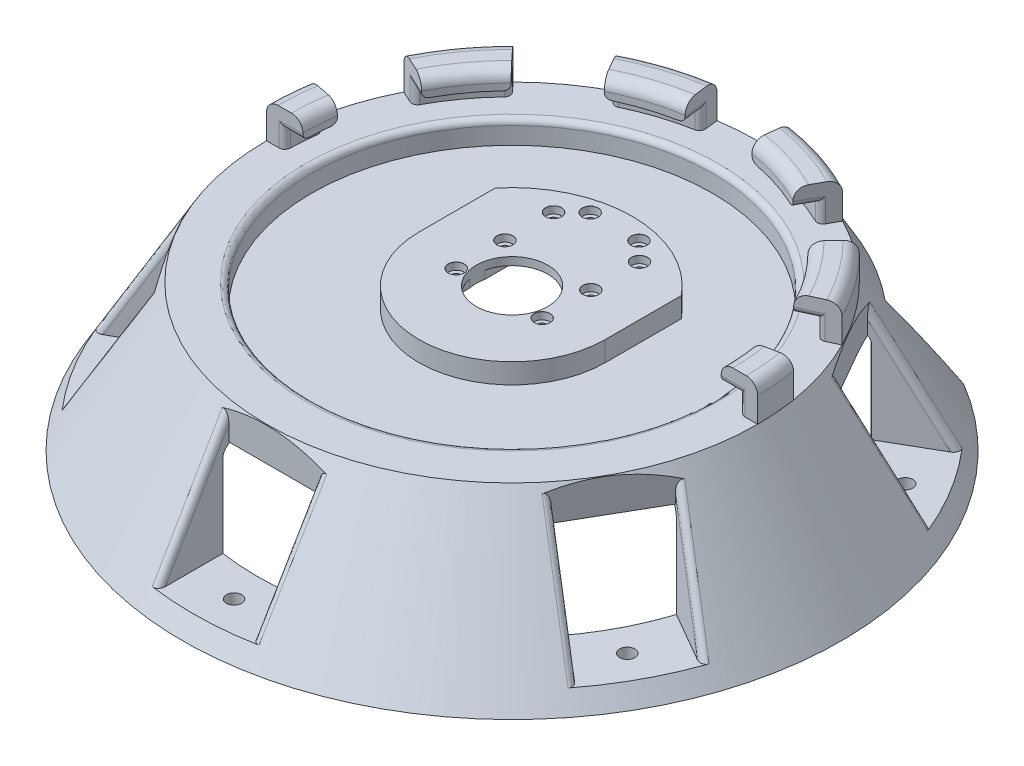
SolidWorks part; units mm, degrees
material "PLA"
ref_plane "Front Plane" through (0, 0, 0) normal (0, 0, 1) x (1, 0, 0)
ref_plane "Top Plane" through (0, 0, 0) normal (0, 1, 0) x (1, 0, 0)
ref_plane "Right Plane" through (0, 0, 0) normal (1, 0, 0) x (0, 0, -1)
sketch "Sketch1" plane through (0, 0, 0) normal (0, 0, 1) x (1, 0, 0)
  line L0 (0, 0) -> (-85.725, 0)
  line L1 (-85.725, 0) -> (-115.0544, -50.8)
  line L2 (-115.0544, -50.8) -> (0, -50.8)
  line L6 (0, 0) -> (0, -50.8) construction
  line L7 (0, 0) -> (0, -50.8)
  dimension "D1" = 85.725
  dimension "D3" = 50.8
  dimension "D4" = 60
revolve "Revolve1" add sketch "Sketch1" angle 360 about L6
sketch "Sketch2" plane through (0, 0, 0) normal (0, 1, 0) x (1, 0, 0)
  circle A0 centre (0, 0) radius 12.5
  dimension "D1" = 25
extrude "Cut-Extrude1" cut sketch "Sketch2" against normal through all
sketch "Sketch3" plane through (0, 0, 0) normal (0, 1, 0) x (1, 0, 0)
  line L0 (-32.5, 0) -> (-32.5, 26.6036)
  line L1 (-32.5, 26.6036) -> (32.5, 26.6036)
  line L2 (32.5, 26.6036) -> (32.5, 0)
  circle A0 centre (0, 0) radius 32.5
  circle A1 centre (0, 0) radius 70
  circle A2 centre (0, 0) radius 42
  circle M1 centre (0, 0) radius 12.5
  dimension "D1" = 65
  dimension "D2" = 140
  dimension "D3" = 84
extrude "Cut-Extrude2" cut sketch "Sketch3" against normal blind 8 contours A1 A0 L0 L1 L2 | A1 A2 region at (0, 0, 33.5845) region at (-68.0201, 0, 0)
sketch "Sketch7" plane through (0, -50.8, 0) normal (0, -1, 0) x (1, 0, 0)
  line L0 (3.6132, 88.8265) -> (-2.6643, -115.0235) construction
  line L1 (-88.0643, 0) -> (82.7357, 0) construction
  line L2 (-62.6643, -63.0586) -> (-62.6643, -115.0235)
  line L3 (-62.6643, -115.0235) -> (57.3357, -115.0235)
  line L4 (57.3357, -115.0235) -> (57.3357, -67.9399)
  arc A2 (57.3357, -67.9399) -> (-62.6643, -63.0586) centre (0, 0) ccw
  circle A3 centre (0, 0) radius 115.0544 construction
  dimension "D1" = 177.8
  dimension "D2" = 25.4
  dimension "D3" = 25.4
  dimension "D4" = 120
  dimension "D5" = 88.9
extrude "Cut-Extrude5" cut sketch "Sketch7" against normal blind 39 contours L3 L4 A2 L2
sketch "Sketch8" plane through (0, 0, 0) normal (0, 1, 0) x (1, 0, 0)
  line L0 (0, 0) -> (3.123, -115.012) construction
  line L2 (-13.0273, -123.925) -> (18.7227, -123.925)
  line L3 (-13.0273, -123.925) -> (-13.0273, -85.825)
  line L4 (-13.0273, -85.825) -> (18.7227, -85.825)
  line L5 (18.7227, -123.925) -> (18.7227, -85.825)
  line L6 (-13.0273, -123.925) -> (18.7227, -85.825) construction
  line L7 (-13.0273, -85.825) -> (18.7227, -123.925) construction
  arc A0 (-62.6643, 96.4919) -> (57.3357, 99.7504) centre (0, 0) ccw construction
  point P6 (2.8477, -104.875)
  dimension "D1" = 85.825
  dimension "D2" = 38.1
  dimension "D3" = 31.75
extrude "Cut-Extrude6" cut sketch "Sketch8" against normal blind 44.45
pattern_circular "CirPattern2" count 6 over 360 about axis through (0, 0, 0) along (0, 1, 0) of "Cut-Extrude6" reverse direction yes
sketch "Sketch9" plane through (0, 0, 0) normal (0, 1, 0) x (1, 0, 0)
  line L0 (0, 0) -> (3.123, -115.012) construction
  arc A0 (-62.6643, 96.4919) -> (57.3357, 99.7504) centre (0, 0) ccw construction
  circle A1 centre (2.7092, -99.772) radius 2.65
  dimension "D1" = 5.3
  dimension "D2" = 15.24
extrude "Cut-Extrude7" cut sketch "Sketch9" against normal through all
pattern_circular "CirPattern3" count 6 over 360 about axis through (0, 0, 0) along (0, 1, 0) of "Cut-Extrude7"
sketch "Sketch12" plane through (0, 0, 0) normal (0, 0, 1) x (1, 0, 0)
  line L0 (85.725, 0) -> (85.725, 12.7)
  line L1 (85.725, 12.7) -> (73.025, 12.7)
  line L2 (73.025, 12.7) -> (73.025, 6.35)
  line L3 (73.025, 6.35) -> (79.375, 6.35)
  line L4 (79.375, 6.35) -> (79.375, 0)
  line L5 (85.725, 0) -> (-85.725, 0) construction
  line L6 (0, 0) -> (0, 12.7) construction
  line L7 (12.5, 0) -> (-12.5, 0) construction
  line L8 (79.375, 0) -> (85.725, 0)
  point P13 (0, 6.35)
  point P14 (0, 0)
  dimension "D1" = 6.35
  dimension "D2" = 73.025
  dimension "D3" = 79.375
  dimension "D4" = 12.7
  dimension "D5" = 12.7
revolve "Revolve2" add sketch "Sketch12" angle 180 about L6
sketch "Sketch15" plane through (0, -11.8, 0) normal (0, -1, 0) x (1, 0, 0)
  line L0 (0, -1000) -> (0, 49000) construction
  point P1 (-15, 4.5)
  point P4 (-15, -12.5)
  point P5 (-15, -29.5)
  point P6 (-8.5, -35.8)
  point P7 (8.5, -35.8)
  point P8 (15, -29.5)
  point P9 (15, -12.5)
  point P10 (15, 4.5)
  dimension "D1" = 17
  dimension "D2" = 17
  dimension "D3" = 4.5
  dimension "D4" = 15
  dimension "D5" = 8.5
  dimension "D6" = 35.8
sketch "Sketch18" plane through (0, 12.7, 0) normal (0, 1, 0) x (1, 0, 0)
  line L0 (46.6433, 89.7185) -> (70.9138, 72.0849)
  line L1 (0, 201000) -> (0, -249000) construction
  line L2 (-15, 100) -> (-9, 50)
  line L3 (-9, 50) -> (9, 50)
  line L4 (9, 50) -> (15, 100)
  line L5 (-15, 100) -> (15, 100)
  line L6 (36.6704, 35.1608) -> (70.9138, 72.0849)
  line L7 (22.1081, 45.7409) -> (36.6704, 35.1608)
  line L8 (46.6433, 89.7185) -> (22.1081, 45.7409)
  line L9 (90.4704, 45.1675) -> (99.7409, 16.6359)
  line L10 (50.334, 6.8913) -> (99.7409, 16.6359)
  line L11 (44.7717, 24.0104) -> (50.334, 6.8913)
  line L12 (90.4704, 45.1675) -> (44.7717, 24.0104)
  line L13 (99.7409, -16.6359) -> (90.4704, -45.1675)
  line L14 (44.7717, -24.0104) -> (90.4704, -45.1675)
  line L15 (50.334, -6.8913) -> (44.7717, -24.0104)
  line L16 (99.7409, -16.6359) -> (50.334, -6.8913)
  line L17 (70.9138, -72.0849) -> (46.6433, -89.7185)
  line L18 (22.1081, -45.7409) -> (46.6433, -89.7185)
  line L19 (36.6704, -35.1608) -> (22.1081, -45.7409)
  line L20 (70.9138, -72.0849) -> (36.6704, -35.1608)
  line L21 (15, -100) -> (-15, -100)
  line L22 (-9, -50) -> (-15, -100)
  line L23 (9, -50) -> (-9, -50)
  line L24 (15, -100) -> (9, -50)
  line L25 (-46.6433, -89.7185) -> (-70.9138, -72.0849)
  line L26 (-36.6704, -35.1608) -> (-70.9138, -72.0849)
  line L27 (-22.1081, -45.7409) -> (-36.6704, -35.1608)
  line L28 (-46.6433, -89.7185) -> (-22.1081, -45.7409)
  line L29 (-90.4704, -45.1675) -> (-99.7409, -16.6359)
  line L30 (-50.334, -6.8913) -> (-99.7409, -16.6359)
  line L31 (-44.7717, -24.0104) -> (-50.334, -6.8913)
  line L32 (-90.4704, -45.1675) -> (-44.7717, -24.0104)
  line L33 (-99.7409, 16.6359) -> (-90.4704, 45.1675)
  line L34 (-44.7717, 24.0104) -> (-90.4704, 45.1675)
  line L35 (-50.334, 6.8913) -> (-44.7717, 24.0104)
  line L36 (-99.7409, 16.6359) -> (-50.334, 6.8913)
  line L37 (-70.9138, 72.0849) -> (-46.6433, 89.7185)
  line L38 (-22.1081, 45.7409) -> (-46.6433, 89.7185)
  line L39 (-36.6704, 35.1608) -> (-22.1081, 45.7409)
  line L40 (-70.9138, 72.0849) -> (-36.6704, 35.1608)
  point P4 (0, 50)
  point P7 (0, 100)
  point P48 (0, 0)
  dimension "D1" = 18
  dimension "D2" = 50
  dimension "D3" = 30
  dimension "D4" = 50
  dimension "D5" = 10
extrude "Cut-Extrude9" cut sketch "Sketch18" against normal blind 12.7
sketch "Sketch20" plane through (0, -11.8, 0) normal (0, -1, 0) x (1, 0, 0)
  line L0 (-22.5, -33) -> (-12.5, -40)
  line L1 (22.5, 20) -> (-22.5, 20)
  line L2 (22.5, 20) -> (22.5, -40)
  line L3 (22.5, -40) -> (-22.5, -40)
  line L4 (-22.5, 20) -> (-22.5, -40)
  line L5 (22.5, 20) -> (-22.5, -40) construction
  line L6 (22.5, -40) -> (-22.5, 20) construction
  line L7 (-12.5, -40) -> (12.5, -40)
  line L8 (12.5, -40) -> (22.5, -33)
  point P0 (0, -10)
  line M11 (-13.0268, 13) -> (13.0268, 13)
  line M12 (13.0268, 13) -> (13.0268, -34)
  line M13 (13.0268, -34) -> (-13.0268, -34)
  line M14 (-13.0268, -34) -> (-13.0268, 13)
  dimension "D1" = 60
  dimension "D2" = 45
  dimension "D3" = 10
  dimension "D4" = 10
  dimension "D5" = 7
  dimension "D6" = 7
  dimension "D7" = 10
extrude "Cut-Extrude11" cut sketch "Sketch3<3>" against normal blind 1 contours A0 L1 M1 | A0 L1 L0 | L1 A0 | L1 A2 A0 | A0 L2 L1 | A0 region at (-28.056, 0, -14.587) region at (-28.5629, 0, -20.2686) region at (0, 0, -33.9353) region at (28.5629, 0, -20.2686) region at (0, 0, -28.9815)
sketch "Sketch3<3>" plane through (0, 0, 0) normal (0, 1, 0) x (1, 0, 0) same geometry as "Sketch3"
sketch "Sketch22" plane through (0, -1, 0) normal (0, 1, 0) x (1, 0, 0)
  circle A0 centre (-15, 12.5) radius 1.4
  circle A1 centre (-15, 29.5) radius 1.4
  circle A2 centre (-8.5, 35.8) radius 1.4
  circle A3 centre (8.5, 35.8) radius 1.4
  circle A4 centre (15, 29.5) radius 1.4
  circle A5 centre (15, 12.5) radius 1.4
  circle A6 centre (15, -4.5) radius 1.4
  circle A7 centre (-15, -4.5) radius 1.4
hole_wizard "CBORE for M2.5 SHCS1" positions "Sketch23" profile "Sketch24" counterbore size "M2.5" standard "ANSI Metric" end condition through all
sketch "Sketch23" plane through (0, -1, 0) normal (0, 1, 0) x (1, 0, 0)
  point P0 (-15, -4.5)
  point P3 (-15, 12.5)
  point P6 (-15, 29.5)
  point P9 (-8.5, 35.8)
  point P12 (8.5, 35.8)
  point P15 (15, 29.5)
  point P18 (15, 12.5)
  point P21 (15, -4.5)
sketch "Sketch24" plane through (-15, -1, 4.5) normal (1, 0, 0) x (0, 0, 1)
  line L0 (0, 0) -> (0, 49.8)
  line L1 (0, 49.8) -> (1.45, 49.8)
  line L3 (1.45, 49.8) -> (1.45, 2.5)
  line L4 (2.75, 2.5) -> (1.45, 2.5)
  line L5 (2.75, 2.5) -> (2.75, 0.025)
  line L6 (2.75, 0.025) -> (2.775, 0)
  line L7 (2.775, 0) -> (0, 0)
  line L8 (-2.75, 0.025) -> (-2.775, 0) construction
  line L11 (0, -6.35) -> (0, 107.95) construction
  dimension "Thru Hole Dia." = 2.9
  dimension "Thru Hole Depth" = 49.8
  dimension "C'Bore Dia." = 5.5
  dimension "C'Bore Depth" = 2.5
  dimension "Near C'Sink Dia." = 5.55
  dimension "Near C'Sink Angle" = 90
fillet "Fillet1" radius 4 12 edges at (85.4509, 12.7, -6.8497) (69.353, 12.7, -50.3879) (26.4905, 12.7, -81.5293) (-26.4905, 12.7, -81.5293) (-69.353, 12.7, -50.3879) (-85.4509, 12.7, -6.8497) (-72.8088, 12.7, -5.6148) (-59.0785, 12.7, -42.923) (-22.566, 12.7, -69.4509) (22.566, 12.7, -69.4509) (59.0785, 12.7, -42.923) (72.8088, 12.7, -5.6148)
fillet "Fillet2" radius 2 12 edges at (75.2789, 6.35, -11.8112) (76.2, 6.35, 0) (53.9595, 6.35, -53.8033) (67.8444, 6.35, -34.6924) (12.0293, 6.35, -75.2444) (34.4956, 6.35, -67.9447) (-12.0293, 6.35, -75.2444) (-34.4956, 6.35, -67.9447) (-53.9595, 6.35, -53.8033) (-67.8444, 6.35, -34.6924) (-75.2789, 6.35, -11.8112) (-76.2, 6.35, 0)
fillet "Fillet3" radius 2 12 edges at (-78.3963, 4.175, -12.4261) (-56.1201, 4.175, -56.1331) (-70.7278, 4.175, -36.0273) (-12.4079, 4.175, -78.3992) (56.1201, 4.175, -56.1331) (78.3963, 4.175, -12.4261) (-79.375, 4.175, 0) (-36.0437, 4.175, -70.7195) (12.4079, 4.175, -78.3992) (36.0437, 4.175, -70.7195) (70.7278, 4.175, -36.0273) (79.375, 4.175, 0)
fillet "Fillet4" radius 2 10 edges
fillet "Fillet5" radius 2 1 edges at (0, 0, 70)
fillet "Fillet6" radius 4 4 edges at (88.8529, -11.8, -2.8943) (-88.8529, -11.8, 2.8943) (-41.9199, -11.8, 78.396) (46.933, -11.8, 75.5017)
fillet "Fillet7" radius 4 1 edges at (61.7573, -11.8, -63.9472)
fillet "Fillet8" radius 4 1 edges at (-66.2697, -11.8, -59.2583)
fillet "Fillet9" radius 1 2 edges
sketch "Sketch28" plane through (0, -11.8, 0) normal (0, -1, 0) x (1, 0, 0)
  line L0 (9.2, 12) -> (-9.2, 12)
  line L1 (-12.2, 9) -> (-12.2, -30)
  line L2 (-9.2, -33) -> (9.2, -33)
  line L3 (12.2, -30) -> (12.2, 9)
  arc A0 (-9.2, 12) -> (-12.2, 9) centre (-9.2, 9) ccw
  arc A1 (-12.2, -30) -> (-9.2, -33) centre (-9.2, -30) ccw
  arc A2 (9.2, -33) -> (12.2, -30) centre (9.2, -30) ccw
  arc A3 (12.2, 9) -> (9.2, 12) centre (9.2, 9) ccw
extrude "Cut-Extrude12" cut sketch "Sketch28" against normal offset from surface (8.05 mm away) 2.75 up to face at (-15, -1, 7.275)
extrude "Cut-Extrude15" cut sketch "Sketch20" against normal offset from surface (5.3 mm away) 2.75 contours L3 L8 L2 L1 L4 L0 M14 M11 M12 M13 | M11 M14 M13 M12 region at (-21.75, -11.8, -6.5) region at (0, -11.8, -10.5) up to face at (0, -3.75, -23.7441)
